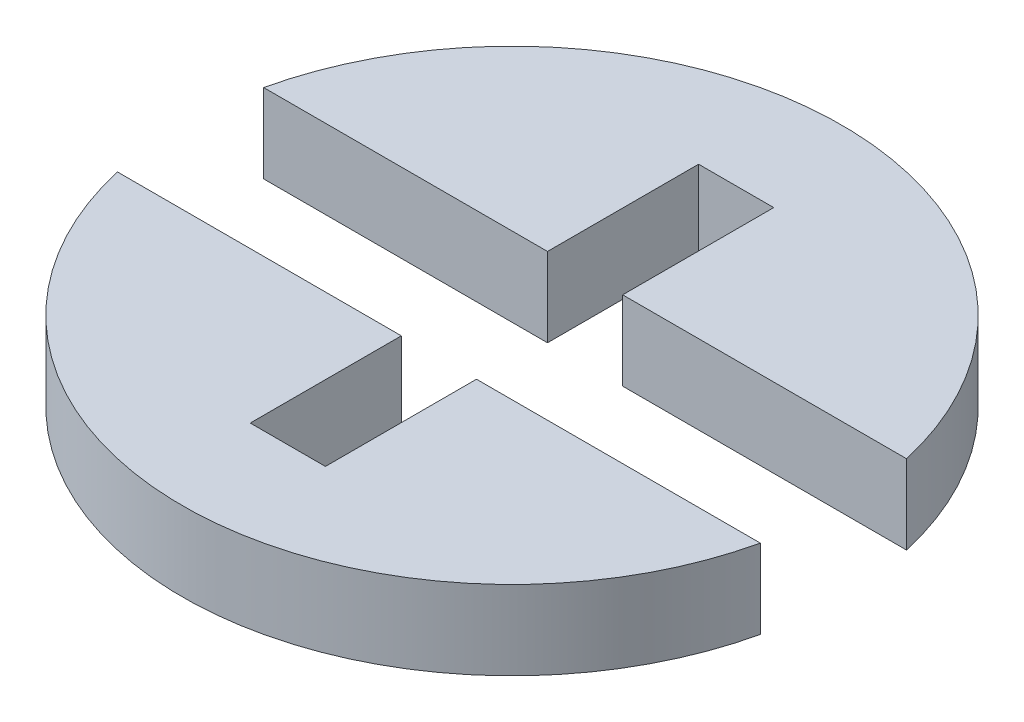
SolidWorks part; units mm, degrees
ref_plane "Front Plane" through (0, 0, 0) normal (0, 0, 1) x (1, 0, 0)
ref_plane "Top Plane" through (0, 0, 0) normal (0, 1, 0) x (1, 0, 0)
ref_plane "Right Plane" through (0, 0, 0) normal (1, 0, 0) x (0, 0, -1)
sketch "Sketch1" plane through (0, 0, 0) normal (0, 1, 0) x (1, 0, 0)
  line L0 (0, -12.5) -> (0, 12.5) construction
  line L1 (0, -12.5) -> (0, 12.5) construction
  line L3 (-1.425, 8.5) -> (1.425, 8.5)
  line L4 (-1.425, 8.5) -> (-1.425, -8.5)
  line L5 (-1.425, -8.5) -> (1.425, -8.5)
  line L6 (1.425, 8.5) -> (1.425, -8.5)
  line L7 (0, -8.5) -> (0, 8.5) construction
  line L8 (-1.425, 0) -> (1.425, 0) construction
  circle A0 centre (0, 0) radius 12.5
  dimension "D1" = 2.85
extrude "Boss-Extrude1" add sketch "Sketch1" along normal blind 1.5 and the other way blind 1.5
sketch "Sketch4" plane through (0, 0, 0) normal (1, 0, 0) x (0, 0, -1)
  line L0 (8.5, -1.425) -> (8.5, 1.425) construction
  line L1 (2.7713, -1.6) -> (2.7713, 1.6)
  line L2 (2.7713, 1.6) -> (0, 3.2)
  line L3 (0, 3.2) -> (-2.7713, 1.6)
  line L4 (-2.7713, 1.6) -> (-2.7713, -1.6)
  line L5 (-2.7713, -1.6) -> (0, -3.2)
  line L6 (0, -3.2) -> (2.7713, -1.6)
  circle A0 centre (0, 0) radius 2.7713 construction
  dimension "D1" = 3.2
extrude "Cut-Extrude1" cut sketch "Sketch4" against normal through all both and the other way through all
